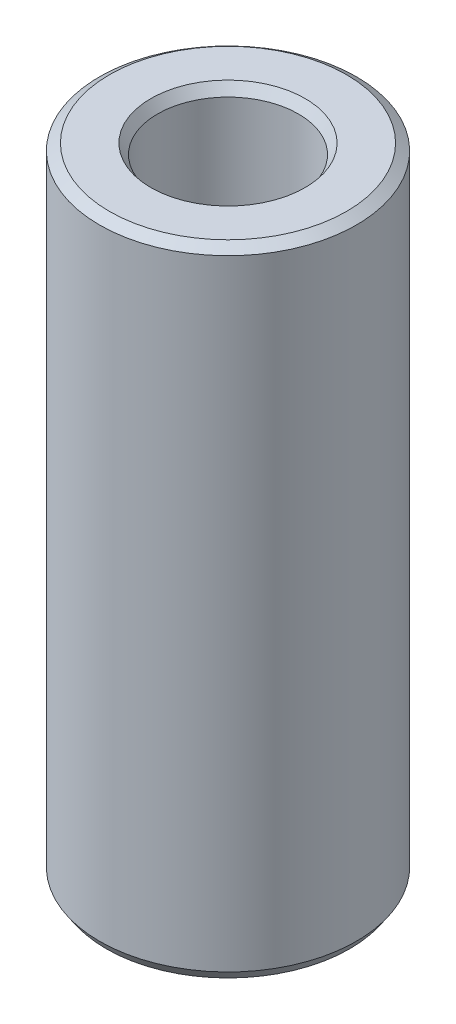
SolidWorks part; units mm, degrees
ref_plane "Front Plane" through (0, 0, 0) normal (0, 0, 1) x (1, 0, 0)
ref_plane "Top Plane" through (0, 0, 0) normal (0, 1, 0) x (1, 0, 0)
ref_plane "Right Plane" through (0, 0, 0) normal (1, 0, 0) x (0, 0, -1)
sketch "Sketch1" plane through (0, 0, 0) normal (0, 1, 0) x (1, 0, 0)
  circle A0 centre (0, 0) radius 47.5
  dimension "SLEEVE_OD" = 95
extrude "Boss-Extrude1" add sketch "Sketch1" along normal blind 235.5605
sketch "Sketch2" plane through (0, 0, 0) normal (0, 1, 0) x (1, 0, 0)
  circle A0 centre (0, 0) radius 26.045
  dimension "BORE_D" = 52.0899
extrude "Cut-Extrude1" cut sketch "Sketch2" along normal through all
chamfer "Chamfer1" distance 2.4955 angle 55.878 4 edges at (0, 235.5605, 26.045) (0, 0, 26.045) (0, 0, 47.5) (0, 235.5605, 47.5) first distance on face at (0, 235.5605, 26.045) first distance on face at (0, 0, 26.045) first distance on face at (0, 235.5605, 47.5)
